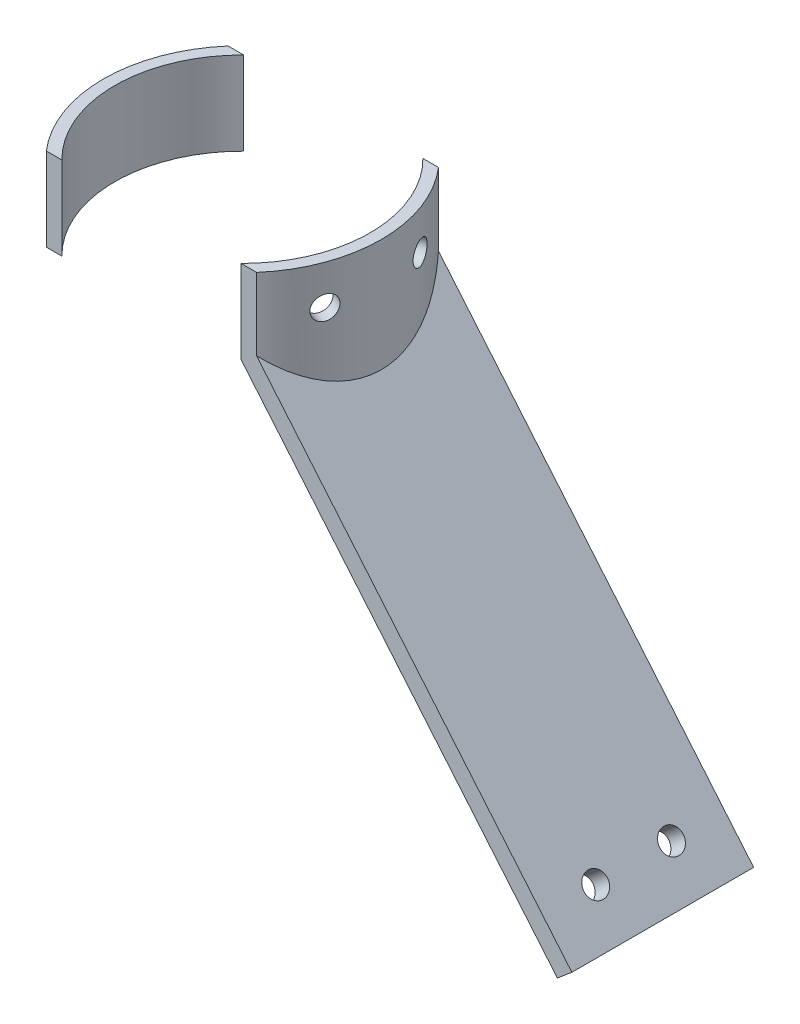
SolidWorks part; units mm, degrees
ref_plane "Front Plane" through (0, 0, 0) normal (0, 0, 1) x (1, 0, 0)
ref_plane "Top Plane" through (0, 0, 0) normal (0, 1, 0) x (1, 0, 0)
ref_plane "Right Plane" through (0, 0, 0) normal (1, 0, 0) x (0, 0, -1)
ref_plane "Plane1" through (0, 3.8, 0) normal (0, 1, 0) x (1, 0, 0)
sketch "Sketch1" plane through (0, 3.8, 0) normal (0, 1, 0) x (1, 0, 0)
  line L0 (13.8825, 12) -> (11.8289, 12)
  line L1 (13.8825, -12) -> (11.8289, -12)
  line L2 (-11.8289, -12) -> (-13.8825, -12)
  line L3 (-11.8289, 12) -> (-13.8825, 12)
  arc A2 (13.8825, -12) -> (13.8825, 12) centre (0, 0) ccw
  arc A3 (11.8289, -12) -> (11.8289, 12) centre (0, 0) ccw
  arc A4 (-11.8289, 12) -> (-11.8289, -12) centre (0, 0) ccw
  arc A5 (-13.8825, 12) -> (-13.8825, -12) centre (0, 0) ccw
  dimension "D2" = 33.7
  dimension "D1" = 36.7
  dimension "D3" = 12
  dimension "D4" = 12
extrude "Boss-Extrude1" add sketch "Sketch1" along normal blind 10 and the other way blind 1 contours A3 L0 A2 L1 | A3 L1 A2 L0 | L2 A5 L3 A4 region at (18.1013, 3.8, 0)
ref_plane "Plane2" through (8.3276, 6.9783, 0) normal (0.7665, 0.6423, 0) x (0, 0, -1)
sketch "Sketch3" plane through (8.3276, 6.9783, 0) normal (0.7665, 0.6423, 0) x (0, 0, -1)
  line L0 (-12, -6.7703) -> (-12, -5.4513) construction
  line L1 (12, -6.7703) -> (12, -5.4513) construction
  line L2 (-12, -6.7703) -> (-12, -5.4513)
  line L3 (12, -6.7703) -> (12, -5.4513)
  line L4 (-12, -5.4513) -> (-12, -70.4513)
  line L5 (-12, -70.4513) -> (12, -70.4513)
  line L6 (12, -70.4513) -> (12, -5.4513)
  line L7 (12, -5.4513) -> (-12, -5.4513)
  dimension "D1" = 65
extrude "Boss-Extrude2" add sketch "Sketch3" along normal blind 2.5 contours L3 L7 L2 L4 L5 L6 region at (32.7029, -22.1103, 0)
sketch "Sketch4" plane through (0, 2.8, 0) normal (0, -1, 0) x (1, 0, 0)
  line L2 (15.0906, 10.4402) -> (15.0906, 7.4965)
  line L3 (15.0906, -7.4965) -> (15.0906, -10.4402)
  line L4 (15.0906, 10.4402) -> (15.0906, 7.4965)
  line L5 (15.0906, -7.4965) -> (15.0906, -10.4402)
  arc A2 (15.0906, -10.4402) -> (15.0906, 10.4402) centre (0, 0) ccw
  arc A3 (15.0906, -7.4965) -> (15.0906, 7.4965) centre (0, 0) ccw
  arc A4 (15.0906, -10.4402) -> (15.0906, 10.4402) centre (0, 0) ccw
  arc A5 (15.0906, -7.4965) -> (15.0906, 7.4965) centre (0, 0) ccw
  dimension "D1" = 0
extrude "Boss-Extrude3" add sketch "Sketch4" along normal up to surface up to face at (22.6733, -6.249, 0)
sketch "Sketch5" plane through (0, 13.8, 0) normal (0, 1, 0) x (1, 0, 0)
  line L0 (11.8289, 12) -> (11.8289, -12)
  arc A0 (11.8289, -12) -> (11.8289, 12) centre (0, 0) ccw construction
  arc A1 (11.8289, -12) -> (11.8289, 12) centre (0, 0) ccw
extrude "Cut-Extrude1" cut sketch "Sketch5" against normal up to surface (11 mm away) up to face at (32.7029, -22.1103, 0)
sketch "Sketch6" plane through (10.2438, 8.584, 0) normal (0.7665, 0.6423, 0) x (0, 0, -1)
  line L0 (-12, -70.4513) -> (12, -70.4513) construction
  line L1 (-12, -70.4513) -> (-12, -5.6652) construction
  circle A0 centre (-5, -64.4513) radius 1.55
  circle A1 centre (5, -64.4513) radius 1.55
  dimension "D1" = 3.1
  dimension "D2" = 3.1
  dimension "D3" = 6
  dimension "D4" = 10
  dimension "D5" = 7
extrude "Cut-Extrude2" cut sketch "Sketch6" against normal up to surface (2.5 mm away) up to face at (33.9582, -23.6083, 0)
ref_plane "Plane3" through (16.1152, 0, -5.8655) normal (0.9397, 0, -0.342) x (0, 1, 0)
sketch "Sketch8" plane through (16.1152, 0, -5.8655) normal (0.9397, 0, -0.342) x (0, 1, 0)
  line L0 (4.2417, -6.5282) -> (13.8, -6.5282) construction
  line L1 (13.8, -6.5282) -> (13.8, 16.0244) construction
  circle A0 centre (8.6, -0.0282) radius 1.55
  dimension "D1" = 3.1
  dimension "D2" = 6.5
  dimension "D3" = 5.2
ref_plane "Plane4" through (16.1152, 0, 5.8655) normal (0.9397, 0, 0.342) x (0, 1, 0)
sketch "Sketch9" plane through (16.1152, 0, 5.8655) normal (0.9397, 0, 0.342) x (0, 1, 0)
  line L0 (4.2417, 6.5282) -> (13.8, 6.5282) construction
  line L1 (13.8, -16.0244) -> (13.8, 6.5282) construction
  circle A0 centre (8.6, 0.0282) radius 1.55
  dimension "D1" = 3.1
  dimension "D2" = 6.5
  dimension "D3" = 5.2
extrude "Cut-Extrude3" cut sketch "Sketch9" against normal blind 2.5 and the other way blind 2.5 contours A0
extrude "Cut-Extrude4" cut sketch "Sketch8" against normal blind 2.5 and the other way blind 2.5 contours A0
